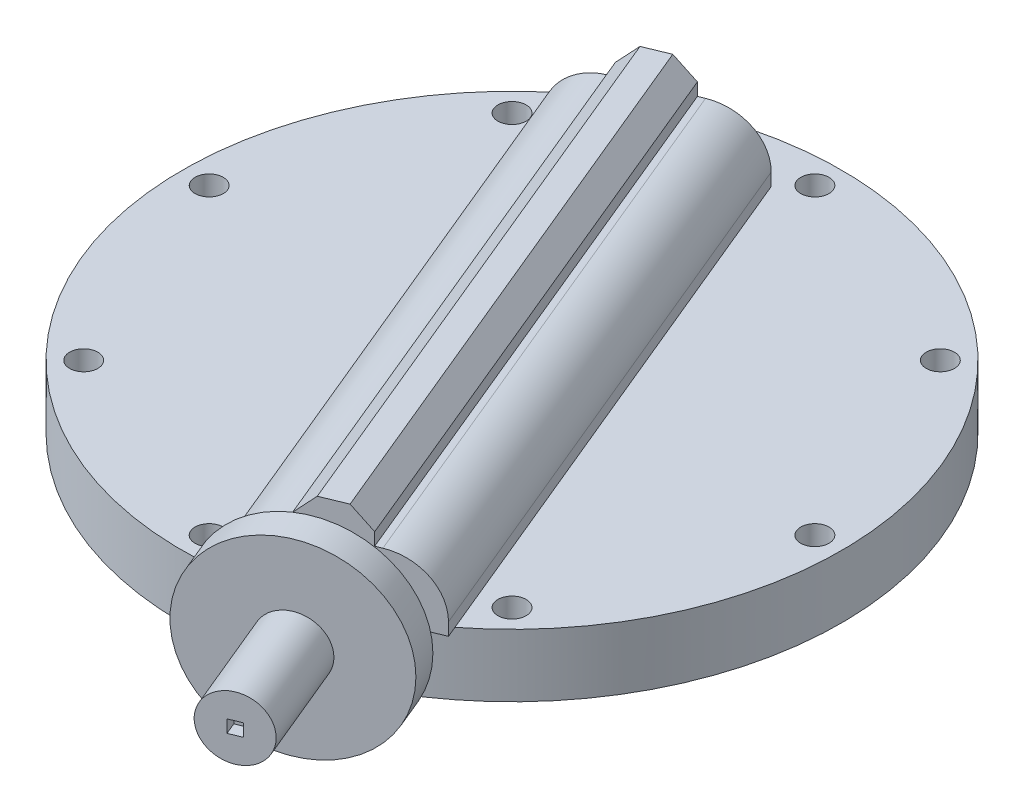
SolidWorks part; units mm, degrees
ref_plane "Front Plane" through (0, 0, 0) normal (0, 0, 1) x (1, 0, 0)
ref_plane "Top Plane" through (0, 0, 0) normal (0, 1, 0) x (1, 0, 0)
ref_plane "Right Plane" through (0, 0, 0) normal (1, 0, 0) x (0, 0, -1)
sketch "Sketch1" plane through (0, 0, 0) normal (0, 1, 0) x (1, 0, 0)
  circle A0 centre (0, 0) radius 66.675
  dimension "D1" = 133.35
extrude "Boss-Extrude1" add sketch "Sketch1" along normal blind 12.7
sketch "Sketch2" plane through (0, 12.7, 0) normal (0, 1, 0) x (1, 0, 0)
  line L0 (0, 0) -> (0, 66.675) construction
  circle A0 centre (0, 0) radius 66.675 construction
  circle A1 centre (0, 61.2775) radius 2.8575
  dimension "D1" = 5.715
  dimension "D2" = 5.3975
extrude "Cut-Extrude1" cut sketch "Sketch2" against normal through all both and the other way through all
pattern_circular "CirPattern1" count 8 over 360 about axis through (0, 12.7, 0) along (0, 1, 0) of "Cut-Extrude1"
sketch "Sketch4" plane through (0, 12.7, 0) normal (0, 1, 0) x (1, 0, 0)
  line L0 (-66.675, 0) -> (66.675, 0) construction
  line L1 (0, 66.675) -> (0, -66.675) construction
  line L2 (-31.5631, 76.2) -> (31.5631, -76.2) construction
  line L3 (-37.0819, 43.0623) -> (-4.2288, 56.6705)
  line L4 (-37.0819, 43.0623) -> (9.0888, -68.4038)
  line L5 (-4.2288, 56.6705) -> (41.942, -54.7956)
  line L6 (9.0888, -68.4038) -> (41.942, -54.7956)
  circle A0 centre (0, 0) radius 66.675 construction
  point P7 (0, 0)
  point P11 (0, 0)
  point P14 (0, 0)
  point P17 (-20.6553, 49.8664)
  dimension "D4" = 53.975
  dimension "D1" = 67.5
  dimension "D2" = 152.4
  dimension "D3" = 35.56
  dimension "D5" = 120.65
  dimension "D6" = 120.65
extrude "Boss-Extrude2" add sketch "Sketch4" along normal blind 12.7
sketch "Sketch5" plane through (0, 25.4, 0) normal (0, 1, 0) x (1, 0, 0)
  line L0 (-20.6553, 49.8664) -> (25.5154, -61.5997) construction
  line L1 (-4.2288, 56.6705) -> (-37.0819, 43.0623) construction
  line L2 (9.0888, -68.4038) -> (41.942, -54.7956) construction
  line L3 (-26.522, 47.4364) -> (19.6488, -64.0297)
  line L4 (19.6488, -64.0297) -> (31.3821, -59.1696)
  line L5 (31.3821, -59.1696) -> (-14.7887, 52.2964)
  line L6 (-14.7887, 52.2964) -> (-26.522, 47.4364)
  dimension "D1" = 12.7
  dimension "D2" = 6.35
extrude "Boss-Extrude3" add sketch "Sketch5" along normal blind 6.35
chamfer "Chamfer1" distance 3.81 angle 45 2 edges at (8.2967, 31.75, 3.4366) (-3.4366, 31.75, 8.2967)
fillet "Fillet3" radius 10.16 2 edges at (18.8566, 25.4, -0.9375) (-13.9965, 25.4, 12.6707)
ref_plane "Plane1" through (28.9175, 0, 69.813) normal (0.3827, 0, 0.9239) x (0.9239, 0, -0.3827)
sketch "Sketch7" plane through (28.9175, 0, 69.813) normal (0.3827, 0, 0.9239) x (0.9239, 0, -0.3827)
  line L0 (-66.675, 0) -> (66.675, 0) construction
  circle A0 centre (0, 15.875) radius 10.16
  dimension "D1" = 20.32
  dimension "D2" = 15.875
  dimension "D3" = 15.875
extrude "Boss-Extrude4" add sketch "Sketch7" against normal blind 10.16 contours A0
sketch "Sketch8" plane through (28.9175, 0, 69.813) normal (0.3827, 0, 0.9239) x (0.9239, 0, -0.3827)
  line L0 (0, 26.035) -> (0, 15.875) construction
  circle A0 centre (0, 15.875) radius 10.16 construction
  circle A1 centre (0, 15.875) radius 19.05
  dimension "D1" = 38.1
extrude "Boss-Extrude5" add sketch "Sketch8" along normal blind 6.35
sketch "Sketch9" plane through (31.3475, 0, 75.6796) normal (0.3827, 0, 0.9239) x (0.9239, 0, -0.3827)
  circle A0 centre (0, 15.875) radius 6.35
  dimension "D1" = 12.7
extrude "Boss-Extrude6" add sketch "Sketch9" along normal blind 21.59
sketch "Sketch10" plane through (39.6096, 0, 95.6262) normal (0.3827, 0, 0.9239) x (0.9239, 0, -0.3827)
  line L0 (0, 9.525) -> (0, 22.225) construction
  circle A0 centre (0, 15.875) radius 6.35 construction
sketch "Sketch11" plane through (39.6096, 0, 95.6262) normal (0.3827, 0, 0.9239) x (0.9239, 0, -0.3827)
  line L1 (-1.27, 17.145) -> (1.27, 17.145)
  line L2 (-1.27, 17.145) -> (-1.27, 14.605)
  line L3 (-1.27, 14.605) -> (1.27, 14.605)
  line L4 (1.27, 17.145) -> (1.27, 14.605)
  line L5 (-1.27, 17.145) -> (1.27, 14.605) construction
  line L6 (-1.27, 14.605) -> (1.27, 17.145) construction
  point P0 (0, 15.875)
  dimension "D1" = 2.54
  dimension "D2" = 2.54
extrude "Cut-Extrude2" cut sketch "Sketch11" against normal blind 2.54 contours L2 L3 L4 L1
